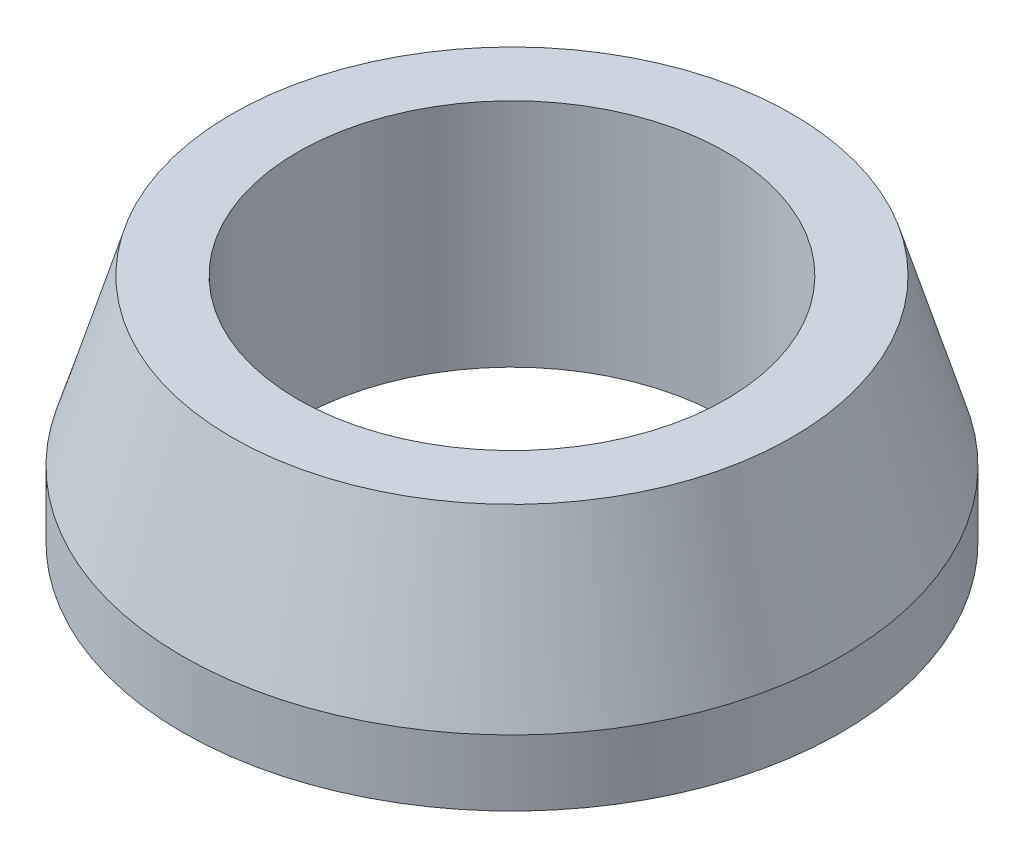
SolidWorks part; units mm, degrees
ref_plane "Płaszczyzna przednia" through (0, 0, 0) normal (0, 0, 1) x (1, 0, 0)
ref_plane "Płaszczyzna górna" through (0, 0, 0) normal (0, 1, 0) x (1, 0, 0)
ref_plane "Płaszczyzna prawa" through (0, 0, 0) normal (1, 0, 0) x (0, 0, -1)
sketch "Sketch1" plane through (0, 0, 0) normal (0, 1, 0) x (1, 0, 0)
  circle A0 centre (0, 0) radius 8.5
  circle A1 centre (0, 0) radius 6.5
  dimension "D1" = 13
  dimension "D2" = 17
ref_plane "Plane1" through (0, -5, 0) normal (0, 1, 0) x (1, 0, 0)
sketch "Sketch2" plane through (0, -5, 0) normal (0, 1, 0) x (1, 0, 0)
  circle A0 centre (0, 0) radius 6.5
  circle A1 centre (0, 0) radius 10
  dimension "D1" = 13
  dimension "D2" = 20
extrude "Boss-Extrude1" add sketch "Sketch2" against normal blind 2
loft "Loft6" add section edge at (0, -5, 10) section "Sketch1" connector at (9.5426, -5, 2.9899) connector at (8.1474, 0, 2.4227)
sketch "Sketch4" plane through (0, -5, 0) normal (0, -1, 0) x (1, 0, 0)
  circle A0 centre (0, 0) radius 6.5
  dimension "D1" = 13
extrude "Cut-Extrude1" cut sketch "Sketch4" against normal through all
equation "\"D1\"=13"
